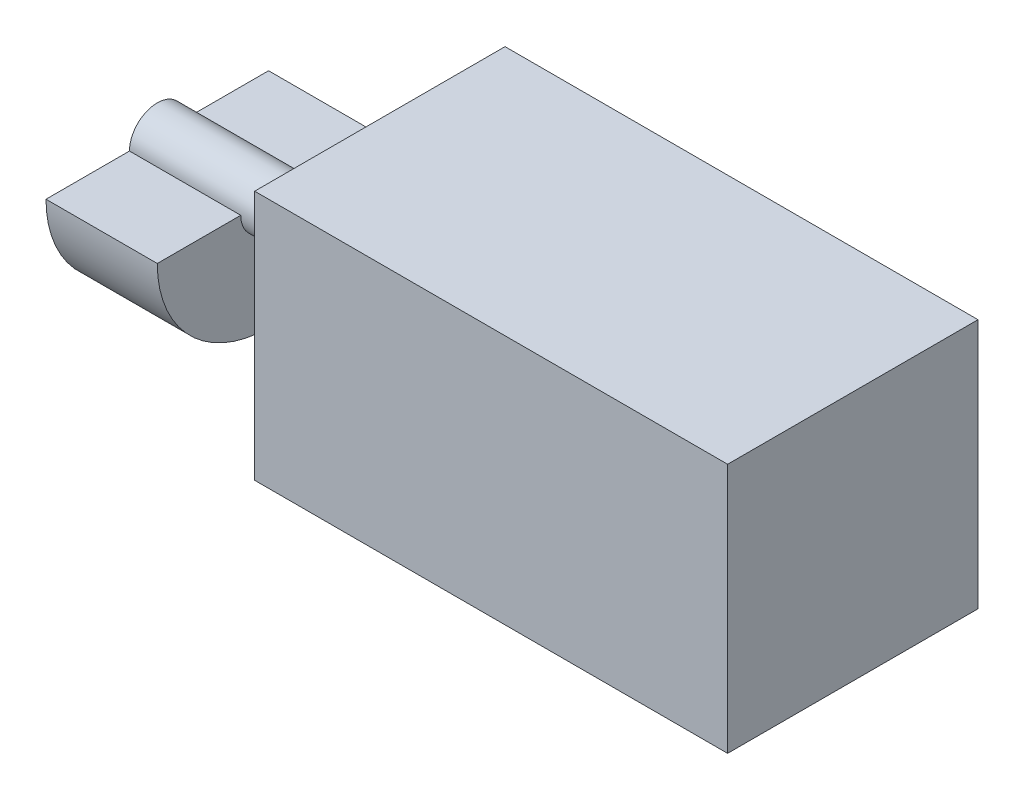
SolidWorks part; units mm, degrees
ref_plane "Front Plane" through (0, 0, 0) normal (0, 0, 1) x (1, 0, 0)
ref_plane "Top Plane" through (0, 0, 0) normal (0, 1, 0) x (1, 0, 0)
ref_plane "Right Plane" through (0, 0, 0) normal (1, 0, 0) x (0, 0, -1)
sketch "Sketch1" plane through (0, 0, 0) normal (0, 1, 0) x (1, 0, 0)
  line L1 (4.25, 2.25) -> (-4.25, 2.25)
  line L2 (4.25, 2.25) -> (4.25, -2.25)
  line L3 (4.25, -2.25) -> (-4.25, -2.25)
  line L4 (-4.25, 2.25) -> (-4.25, -2.25)
  line L5 (4.25, 2.25) -> (-4.25, -2.25) construction
  line L6 (4.25, -2.25) -> (-4.25, 2.25) construction
  point P0 (0, 0)
  dimension "D1" = 4.5
  dimension "D2" = 8.5
extrude "Boss-Extrude1" add sketch "Sketch1" along normal blind 4.5
sketch "Sketch2" plane through (-4.25, 0, 0) normal (-1, 0, 0) x (0, 0, 1)
  line L0 (-2.25, 0) -> (2.25, 4.5) construction
  circle A0 centre (0, 2.25) radius 1.25
  dimension "D1" = 2.5
extrude "Boss-Extrude2" add sketch "Sketch2" along normal blind 1
sketch "Sketch3" plane through (-5.25, 0, 0) normal (-1, 0, 0) x (0, 0, 1)
  circle A0 centre (0, 2.25) radius 0.5
  dimension "D1" = 1
extrude "Boss-Extrude3" add sketch "Sketch3" along normal blind 1
sketch "Sketch4" plane through (-6.25, 0, 0) normal (-1, 0, 0) x (0, 0, 1)
  circle A0 centre (0, 2.25) radius 2
  dimension "D1" = 4
extrude "Boss-Extrude4" add sketch "Sketch4" along normal blind 2
sketch "Sketch5" plane through (-8.25, 0, 0) normal (-1, 0, 0) x (0, 0, 1)
  line L0 (-2, 2.25) -> (-0.5, 2.25)
  line L1 (0.5, 2.25) -> (2, 2.25)
  circle A0 centre (0, 2.25) radius 0.5
  circle A1 centre (0, 2.25) radius 2 construction
  circle A2 centre (0, 2.25) radius 2
  circle M1 centre (0, 2.25) radius 2
  dimension "D1" = 1
extrude "Cut-Extrude1" cut sketch "Sketch5" against normal blind 2 contours A0 L1 L0 M1 region at (-8.25, 3.1413, 0)
